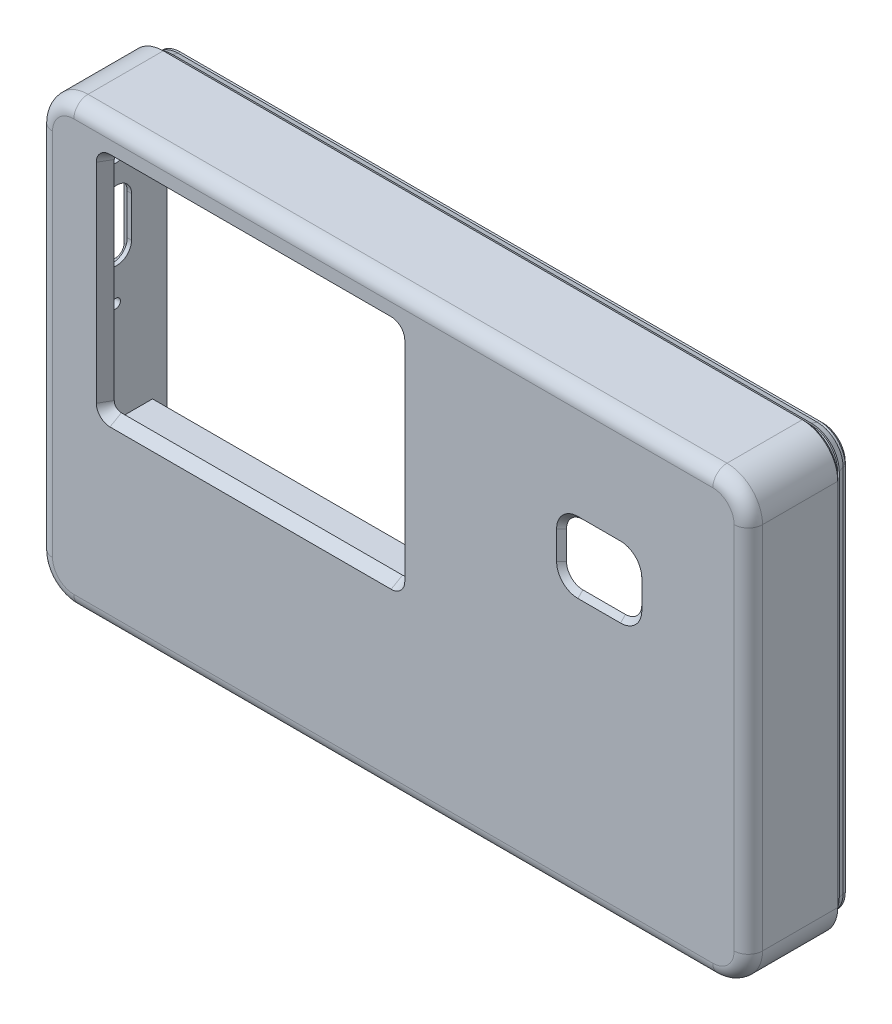
SolidWorks part; units mm, degrees
ref_plane "Front Plane" through (0, 0, 0) normal (0, 0, 1) x (1, 0, 0)
ref_plane "Top Plane" through (0, 0, 0) normal (0, 1, 0) x (1, 0, 0)
ref_plane "Right Plane" through (0, 0, 0) normal (1, 0, 0) x (0, 0, -1)
sketch "Body_Sk1" plane through (0, 0, 0) normal (0, 0, 1) x (1, 0, 0)
  line L0 (-45, -31) -> (45, -31)
  line L1 (50, -26) -> (50, 26)
  line L2 (45, 31) -> (-45, 31)
  line L3 (-50, 26) -> (-50, -26)
  arc A0 (-50, -26) -> (-45, -31) centre (-45, -26) ccw
  arc A1 (45, -31) -> (50, -26) centre (45, -26) ccw
  arc A2 (50, 26) -> (45, 31) centre (45, 26) ccw
  arc A3 (-45, 31) -> (-50, 26) centre (-45, 26) ccw
extrude "Body" add sketch "Body_Sk1" against normal blind 13
fillet "Round_Front" radius 2 8 edges at (-48.5355, -29.5355, 0) (0, -31, 0) (48.5355, -29.5355, 0) (50, 0, 0) (48.5355, 29.5355, 0) (0, 31, 0) (-48.5355, 29.5355, 0) (-50, 0, 0)
ref_plane "PZ_m13_00" through (0, 0, -13) normal (0, 0, 1) x (1, 0, 0)
sketch "Cavity_Sk2" plane through (0, 0, -13) normal (0, 0, 1) x (1, 0, 0)
  line L0 (-45, -28.4) -> (45, -28.4)
  line L1 (47.4, -26) -> (47.4, 26)
  line L2 (45, 28.4) -> (-45, 28.4)
  line L3 (-47.4, 26) -> (-47.4, -26)
  arc A0 (-47.4, -26) -> (-45, -28.4) centre (-45, -26) ccw
  arc A1 (45, -28.4) -> (47.4, -26) centre (45, -26) ccw
  arc A2 (47.4, 26) -> (45, 28.4) centre (45, 26) ccw
  arc A3 (-45, 28.4) -> (-47.4, 26) centre (-45, 26) ccw
extrude "Cavity" cut sketch "Cavity_Sk2" along normal blind 11.4
sketch "Lip_Sk3" plane through (0, 0, -13) normal (0, 0, 1) x (1, 0, 0)
  line L0 (-45, -29.66) -> (45, -29.66)
  line L1 (48.66, -26) -> (48.66, 26)
  line L2 (45, 29.66) -> (-45, 29.66)
  line L3 (-48.66, 26) -> (-48.66, -26)
  line L4 (-45, -28.4) -> (45, -28.4)
  line L5 (47.4, -26) -> (47.4, 26)
  line L6 (45, 28.4) -> (-45, 28.4)
  line L7 (-47.4, 26) -> (-47.4, -26)
  arc A0 (-48.66, -26) -> (-45, -29.66) centre (-45, -26) ccw
  arc A1 (45, -29.66) -> (48.66, -26) centre (45, -26) ccw
  arc A2 (48.66, 26) -> (45, 29.66) centre (45, 26) ccw
  arc A3 (-45, 29.66) -> (-48.66, 26) centre (-45, 26) ccw
  arc A4 (-47.4, -26) -> (-45, -28.4) centre (-45, -26) ccw
  arc A5 (45, -28.4) -> (47.4, -26) centre (45, -26) ccw
  arc A6 (47.4, 26) -> (45, 28.4) centre (45, 26) ccw
  arc A7 (-45, 28.4) -> (-47.4, 26) centre (-45, 26) ccw
extrude "Lip" add sketch "Lip_Sk3" against normal blind 2.5
chamfer "Lip_Chamfer" distance 0.5 angle 45 8 edges at (0, -29.66, -15.5) (48.66, 0, -15.5) (47.588, 28.588, -15.5) (0, 29.66, -15.5) (47.588, -28.588, -15.5) (-47.588, 28.588, -15.5) (-47.588, -28.588, -15.5) (-48.66, 0, -15.5)
ref_plane "PZ_m13_90" through (0, 0, -13.9) normal (0, 0, 1) x (1, 0, 0)
sketch "Bead_Sk4" plane through (0, 0, -13.9) normal (0, 0, 1) x (1, 0, 0)
  line L0 (-45, -29.91) -> (45, -29.91)
  line L1 (48.91, -26) -> (48.91, 26)
  line L2 (45, 29.91) -> (-45, 29.91)
  line L3 (-48.91, 26) -> (-48.91, -26)
  line L4 (-45, -29.06) -> (45, -29.06)
  line L5 (48.06, -26) -> (48.06, 26)
  line L6 (45, 29.06) -> (-45, 29.06)
  line L7 (-48.06, 26) -> (-48.06, -26)
  arc A0 (-48.91, -26) -> (-45, -29.91) centre (-45, -26) ccw
  arc A1 (45, -29.91) -> (48.91, -26) centre (45, -26) ccw
  arc A2 (48.91, 26) -> (45, 29.91) centre (45, 26) ccw
  arc A3 (-45, 29.91) -> (-48.91, 26) centre (-45, 26) ccw
  arc A4 (-48.06, -26) -> (-45, -29.06) centre (-45, -26) ccw
  arc A5 (45, -29.06) -> (48.06, -26) centre (45, -26) ccw
  arc A6 (48.06, 26) -> (45, 29.06) centre (45, 26) ccw
  arc A7 (-45, 29.06) -> (-48.06, 26) centre (-45, 26) ccw
extrude "Bead" add sketch "Bead_Sk4" against normal blind 0.8 draft 17.354
sketch "Screen_Window_Sk5" plane through (0, 0, 0) normal (0, 0, 1) x (1, 0, 0)
  line L0 (-39.91, -6.0338) -> (-0.31, -6.0338)
  line L1 (1.6138, -4.11) -> (1.6138, 25.29)
  line L2 (-0.31, 27.2138) -> (-39.91, 27.2138)
  line L3 (-41.8338, 25.29) -> (-41.8338, -4.11)
  arc A0 (-41.8338, -4.11) -> (-39.91, -6.0338) centre (-39.91, -4.11) ccw
  arc A1 (-0.31, -6.0338) -> (1.6138, -4.11) centre (-0.31, -4.11) ccw
  arc A2 (1.6138, 25.29) -> (-0.31, 27.2138) centre (-0.31, 25.29) ccw
  arc A3 (-39.91, 27.2138) -> (-41.8338, 25.29) centre (-39.91, 25.29) ccw
extrude "Screen_Window" cut sketch "Screen_Window_Sk5" against normal blind 1.9 draft 30
ref_plane "PZ_m1_60" through (0, 0, -1.6) normal (0, 0, 1) x (1, 0, 0)
sketch "Board_Fence_Sk6" plane through (0, 0, -1.6) normal (0, 0, 1) x (1, 0, 0)
  line L0 (2.5, -3.92) -> (3.7, -3.92)
  line L1 (3.7, -3.92) -> (3.7, 27.1)
  line L2 (3.7, 27.1) -> (2.5, 27.1)
  line L3 (2.5, 27.1) -> (2.5, -3.92)
  line L4 (-41.42, -8.32) -> (0.8, -8.32)
  line L5 (0.8, -8.32) -> (0.8, -7.12)
  line L6 (0.8, -7.12) -> (-41.42, -7.12)
  line L7 (-41.42, -7.12) -> (-41.42, -8.32)
extrude "Board_Fence" add sketch "Board_Fence_Sk6" against normal blind 5.9
sketch "TP_Rails_Sk7" plane through (0, 0, -1.6) normal (0, 0, 1) x (1, 0, 0)
  line L0 (-45.7, -26.8) -> (-20.7, -26.8)
  line L1 (-20.7, -26.8) -> (-20.7, -25.6)
  line L2 (-20.7, -25.6) -> (-45.7, -25.6)
  line L3 (-45.7, -25.6) -> (-45.7, -26.8)
  line L4 (-45.7, -11.5) -> (-20.7, -11.5)
  line L5 (-20.7, -11.5) -> (-20.7, -10.3)
  line L6 (-20.7, -10.3) -> (-45.7, -10.3)
  line L7 (-45.7, -10.3) -> (-45.7, -11.5)
extrude "TP_Rails" add sketch "TP_Rails_Sk7" against normal blind 1.57
sketch "TP_Fence_Sk8" plane through (0, 0, -1.6) normal (0, 0, 1) x (1, 0, 0)
  line L0 (-43.2, -9.75) -> (-19.2, -9.75)
  line L1 (-19.2, -9.75) -> (-19.2, -8.75)
  line L2 (-19.2, -8.75) -> (-43.2, -8.75)
  line L3 (-43.2, -8.75) -> (-43.2, -9.75)
  line L4 (-18.9, -26.2) -> (-17.9, -26.2)
  line L5 (-17.9, -26.2) -> (-17.9, -10.9)
  line L6 (-17.9, -10.9) -> (-18.9, -10.9)
  line L7 (-18.9, -10.9) -> (-18.9, -26.2)
  line L8 (-43.2, -28.4) -> (-19.2, -28.4)
  line L9 (-19.2, -28.4) -> (-19.2, -27.35)
  line L10 (-19.2, -27.35) -> (-43.2, -27.35)
  line L11 (-43.2, -27.35) -> (-43.2, -28.4)
extrude "TP_Fence" add sketch "TP_Fence_Sk8" against normal blind 3.37
sketch "Cell_Ribs_Sk9" plane through (0, 0, -1.6) normal (0, 0, 1) x (1, 0, 0)
  line L0 (-10.6, -24.05) -> (-9.4, -24.05)
  line L1 (-9.4, -24.05) -> (-9.4, -12.05)
  line L2 (-9.4, -12.05) -> (-10.6, -12.05)
  line L3 (-10.6, -12.05) -> (-10.6, -24.05)
  line L4 (7.4, -24.05) -> (8.6, -24.05)
  line L5 (8.6, -24.05) -> (8.6, -12.05)
  line L6 (8.6, -12.05) -> (7.4, -12.05)
  line L7 (7.4, -12.05) -> (7.4, -24.05)
  line L8 (21.4, -24.05) -> (22.6, -24.05)
  line L9 (22.6, -24.05) -> (22.6, -12.05)
  line L10 (22.6, -12.05) -> (21.4, -12.05)
  line L11 (21.4, -12.05) -> (21.4, -24.05)
extrude "Cell_Ribs" add sketch "Cell_Ribs_Sk9" against normal blind 9.05
sketch "MAX_Relief_Sk10" plane through (0, 0, -1.6) normal (0, 0, 1) x (1, 0, 0)
  line L0 (20.35, 3.85) -> (37.65, 3.85)
  line L1 (38.65, 4.85) -> (38.65, 17.15)
  line L2 (37.65, 18.15) -> (20.35, 18.15)
  line L3 (19.35, 17.15) -> (19.35, 4.85)
  arc A0 (19.35, 4.85) -> (20.35, 3.85) centre (20.35, 4.85) ccw
  arc A1 (37.65, 3.85) -> (38.65, 4.85) centre (37.65, 4.85) ccw
  arc A2 (38.65, 17.15) -> (37.65, 18.15) centre (37.65, 17.15) ccw
  arc A3 (20.35, 18.15) -> (19.35, 17.15) centre (20.35, 17.15) ccw
extrude "MAX_Relief" cut sketch "MAX_Relief_Sk10" along normal blind 0.9
sketch "MAX_Window_Sk11" plane through (0, 0, 0) normal (0, 0, 1) x (1, 0, 0)
  line L0 (26, 7) -> (32, 7)
  line L1 (34, 9) -> (34, 13)
  line L2 (32, 15) -> (26, 15)
  line L3 (24, 13) -> (24, 9)
  arc A0 (24, 9) -> (26, 7) centre (26, 9) ccw
  arc A1 (32, 7) -> (34, 9) centre (32, 9) ccw
  arc A2 (34, 13) -> (32, 15) centre (32, 13) ccw
  arc A3 (26, 15) -> (24, 13) centre (26, 13) ccw
extrude "MAX_Window" cut sketch "MAX_Window_Sk11" against normal blind 1.8
chamfer "MAX_Window_Chamfer" distance 1 angle 45 8 edges at (24.5858, 7.5858, 0) (29, 7, 0) (33.4142, 7.5858, 0) (34, 11, 0) (33.4142, 14.4142, 0) (29, 15, 0) (24.5858, 14.4142, 0) (24, 11, 0)
ref_plane "PZ_m0_70" through (0, 0, -0.7) normal (0, 0, 1) x (1, 0, 0)
sketch "MAX_Ledges_Sk12" plane through (0, 0, -0.7) normal (0, 0, 1) x (1, 0, 0)
  line L0 (18.65, 3.15) -> (20.25, 3.15)
  line L1 (20.25, 3.15) -> (20.25, 4.75)
  line L2 (20.25, 4.75) -> (18.65, 4.75)
  line L3 (18.65, 4.75) -> (18.65, 3.15)
  line L4 (18.65, 17.25) -> (20.25, 17.25)
  line L5 (20.25, 17.25) -> (20.25, 18.85)
  line L6 (20.25, 18.85) -> (18.65, 18.85)
  line L7 (18.65, 18.85) -> (18.65, 17.25)
  line L8 (37.75, 3.15) -> (39.35, 3.15)
  line L9 (39.35, 3.15) -> (39.35, 4.75)
  line L10 (39.35, 4.75) -> (37.75, 4.75)
  line L11 (37.75, 4.75) -> (37.75, 3.15)
  line L12 (37.75, 17.25) -> (39.35, 17.25)
  line L13 (39.35, 17.25) -> (39.35, 18.85)
  line L14 (39.35, 18.85) -> (37.75, 18.85)
  line L15 (37.75, 18.85) -> (37.75, 17.25)
extrude "MAX_Ledges" add sketch "MAX_Ledges_Sk12" against normal blind 1.3
sketch "MAX_Fence_Sk13" plane through (0, 0, -1.6) normal (0, 0, 1) x (1, 0, 0)
  line L0 (17.45, 20.05) -> (37.35, 20.05)
  line L1 (37.35, 20.05) -> (37.35, 18.85)
  line L2 (37.35, 18.85) -> (18.65, 18.85)
  line L3 (18.65, 18.85) -> (18.65, 3.15)
  line L4 (18.65, 3.15) -> (37.35, 3.15)
  line L5 (37.35, 3.15) -> (37.35, 1.95)
  line L6 (37.35, 1.95) -> (17.45, 1.95)
  line L7 (17.45, 1.95) -> (17.45, 20.05)
extrude "MAX_Fence" add sketch "MAX_Fence_Sk13" against normal blind 2.6
ref_plane "PX_m50_00" through (-50, 0, 0) normal (1, 0, 0) x (0, 0, -1)
sketch "USB_Recess_Sk14" plane through (-50, 0, 0) normal (1, 0, 0) x (0, 0, -1)
  line L0 (12.07, 5.29) -> (12.07, 15.89)
  line L1 (10.87, 17.09) -> (6.07, 17.09)
  line L2 (4.87, 15.89) -> (4.87, 5.29)
  line L3 (6.07, 4.09) -> (10.87, 4.09)
  line L4 (9.6, -23.85) -> (9.6, -13.25)
  line L5 (8.4, -12.05) -> (3.6, -12.05)
  line L6 (2.4, -13.25) -> (2.4, -23.85)
  line L7 (3.6, -25.05) -> (8.4, -25.05)
  arc A0 (10.87, 4.09) -> (12.07, 5.29) centre (10.87, 5.29) ccw
  arc A1 (12.07, 15.89) -> (10.87, 17.09) centre (10.87, 15.89) ccw
  arc A2 (6.07, 17.09) -> (4.87, 15.89) centre (6.07, 15.89) ccw
  arc A3 (4.87, 5.29) -> (6.07, 4.09) centre (6.07, 5.29) ccw
  arc A4 (8.4, -25.05) -> (9.6, -23.85) centre (8.4, -23.85) ccw
  arc A5 (9.6, -13.25) -> (8.4, -12.05) centre (8.4, -13.25) ccw
  arc A6 (3.6, -12.05) -> (2.4, -13.25) centre (3.6, -13.25) ccw
  arc A7 (2.4, -23.85) -> (3.6, -25.05) centre (3.6, -23.85) ccw
extrude "USB_Recess" cut sketch "USB_Recess_Sk14" along normal blind 2
sketch "Left_Ports_Sk15" plane through (-50, 0, 0) normal (1, 0, 0) x (0, 0, -1)
  line L0 (6.42, 7.74) -> (6.42, 13.44)
  line L1 (10.52, 13.44) -> (10.52, 7.74)
  line L2 (3.75, -21.2) -> (3.75, -15.9)
  line L3 (8.25, -15.9) -> (8.25, -21.2)
  arc A0 (6.42, 13.44) -> (10.52, 13.44) centre (8.47, 13.44) cw
  arc A1 (10.52, 7.74) -> (6.42, 7.74) centre (8.47, 7.74) cw
  arc A2 (3.75, -15.9) -> (8.25, -15.9) centre (6, -15.9) cw
  arc A3 (8.25, -21.2) -> (3.75, -21.2) centre (6, -21.2) cw
  circle A4 centre (8.305, 20.04) radius 1.8
  circle A5 centre (8.305, 1.115) radius 0.65
extrude "Left_Ports" cut sketch "Left_Ports_Sk15" along normal blind 3.2
sketch "Buzzer_Keeper_Sk16" plane through (0, 0, -1.6) normal (0, 0, 1) x (1, 0, 0)
  line L0 (44.3, -22) -> (45.5, -22)
  line L1 (45.5, -22) -> (45.5, -14)
  line L2 (45.5, -14) -> (44.3, -14)
  line L3 (44.3, -14) -> (44.3, -22)
extrude "Buzzer_Keeper" add sketch "Buzzer_Keeper_Sk16" against normal blind 14.8
sketch "Mic_Keeper_Sk17" plane through (0, 0, -1.6) normal (0, 0, 1) x (1, 0, 0)
  line L0 (13, 27.2) -> (19, 27.2)
  line L1 (19, 27.2) -> (19, 28.4)
  line L2 (19, 28.4) -> (13, 28.4)
  line L3 (13, 28.4) -> (13, 27.2)
extrude "Mic_Keeper" add sketch "Mic_Keeper_Sk17" against normal blind 13.5
chamfer "Seam_Shadow" distance 0.4 angle 45 8 edges at (0, -31, -13) (50, 0, -13) (48.5355, 29.5355, -13) (0, 31, -13) (48.5355, -29.5355, -13) (-48.5355, 29.5355, -13) (-48.5355, -29.5355, -13) (-50, 0, -13)
ref_plane "PY_m31_00" through (0, -31, 0) normal (0, 1, 0) x (1, 0, 0)
sketch "Pry_Notch_Sk18" plane through (0, -31, 0) normal (0, 1, 0) x (1, 0, 0)
  line L0 (34, 13) -> (42, 13)
  line L1 (42, 13) -> (42, 11.2)
  line L2 (42, 11.2) -> (34, 11.2)
  line L3 (34, 11.2) -> (34, 13)
extrude "Pry_Notch" cut sketch "Pry_Notch_Sk18" along normal blind 1.2
